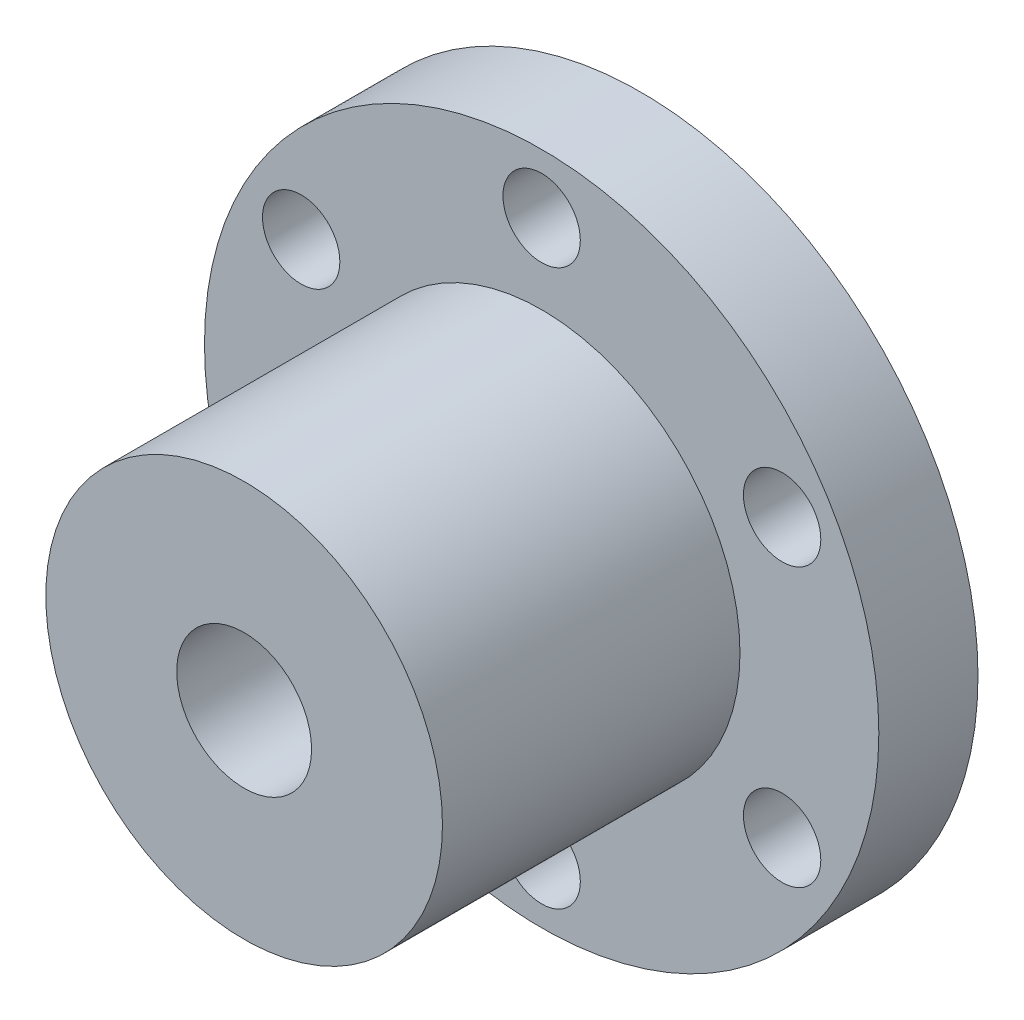
SolidWorks part; units mm, degrees
ref_plane "Alzado" through (0, 0, 0) normal (0, 0, 1) x (1, 0, 0)
ref_plane "Planta" through (0, 0, 0) normal (0, 1, 0) x (1, 0, 0)
ref_plane "Vista lateral" through (0, 0, 0) normal (1, 0, 0) x (0, 0, -1)
sketch "Croquis1" plane through (0, 0, 0) normal (0, 1, 0) x (1, 0, 0)
  line L0 (0, 0) -> (0, 61.4263) construction
  line L1 (0, 0) -> (17, 0)
  line L2 (17, 0) -> (17, -5)
  line L3 (17, -5) -> (10, -5)
  line L4 (10, -5) -> (10, -20)
  line L5 (10, -20) -> (0, -20)
  line L6 (0, -20) -> (0, 0)
  dimension "D1" = 17
  dimension "D2" = 5
  dimension "D3" = 20
  dimension "D4" = 10
revolve "Revolución1" add sketch "Croquis1" angle 360 about L0
hole_wizard "Taladro roscado M81" positions "Croquis3" profile "Croquis2" tap size "M8" standard "Is"
sketch "Croquis3" plane through (0, 0, 20) normal (0, 0, 1) x (1, 0, 0)
  point P0 (0, 0)
sketch "Croquis2" plane through (0, 0, 20) normal (1, 0, 0) x (0, -1, 0)
  line L0 (0, 0) -> (0, 24.2929)
  line L1 (0, 24.2929) -> (3.4, 22.25)
  line L2 (3.4, 22.25) -> (3.4, 0)
  line L5 (3.4, 0) -> (0, 0)
  line L10 (0, 24.2929) -> (-3.4, 22.25) construction
  line L11 (0, -6.35) -> (0, 107.95) construction
  dimension "Diámetro de perforador para roscar" = 6.8
  dimension "Profundidad de perforador para roscar" = 22.25
  dimension "Ángulo de perforador" = 118
cosmetic thread "Rosca de taladro1" parameters "D1"=16, "D2"=8
hole_wizard "Taladro de margen para M3.51" positions "Croquis5" profile "Croquis4" hole size "M3.5" standard "Ansi Metric"
sketch "Croquis5" plane through (0, 0, 0) normal (0, 0, -1) x (-1, 0, 0)
  line L0 (0, 14) -> (0, 0) construction
  point P0 (0, 14)
  dimension "D1" = 14
sketch "Croquis4" plane through (0, 14, 0) normal (1, 0, 0) x (0, 1, 0)
  line L0 (0, 0) -> (0, 501.1717)
  line L1 (0, 501.1717) -> (1.95, 500)
  line L2 (1.95, 500) -> (1.95, 0)
  line L5 (1.95, 0) -> (0, 0)
  line L10 (0, 501.1717) -> (-1.95, 500) construction
  line L11 (0, -6.35) -> (0, 107.95) construction
  dimension "Diámetro de taladro" = 3.9
  dimension "Profundidad de taladro" = 500
  dimension "Ángulo de perforador" = 118
ref_axis "Eje1" through (0, 0, 0) along (0, 0, 1)
pattern_circular "MatrizC1" count 6 over 360 about axis through (0, 0, 0) along (0, 0, 1) of "Taladro de margen para M3.51"
